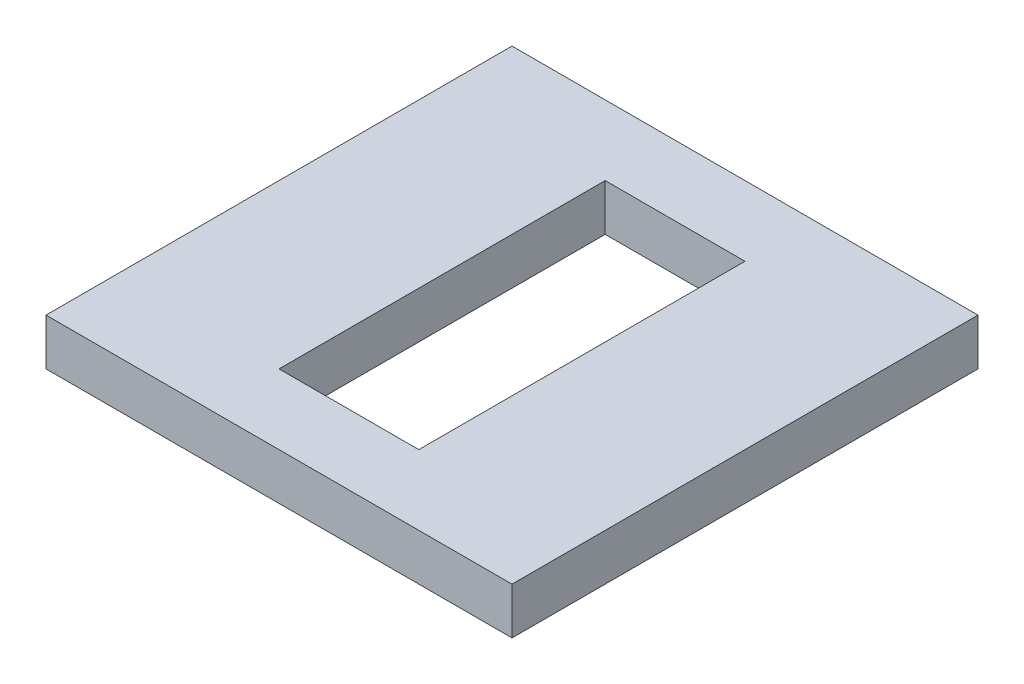
SolidWorks part; units mm, degrees
ref_plane "Front Plane" through (0, 0, 0) normal (0, 0, 1) x (1, 0, 0)
ref_plane "Top Plane" through (0, 0, 0) normal (0, 1, 0) x (1, 0, 0)
ref_plane "Right Plane" through (0, 0, 0) normal (1, 0, 0) x (0, 0, -1)
sketch "Sketch1" plane through (0, 0, 0) normal (0, 1, 0) x (1, 0, 0)
  line L1 (-49.3023, 40.5814) -> (50.6977, 40.5814)
  line L2 (-49.3023, 40.5814) -> (-49.3023, -59.4186)
  line L3 (-49.3023, -59.4186) -> (50.6977, -59.4186)
  line L4 (50.6977, 40.5814) -> (50.6977, -59.4186)
  line L5 (-14.3023, 25.5814) -> (15.6977, 25.5814)
  line L6 (-14.3023, 25.5814) -> (-14.3023, -44.4186)
  line L7 (-14.3023, -44.4186) -> (15.6977, -44.4186)
  line L8 (15.6977, 25.5814) -> (15.6977, -44.4186)
  dimension "D1" = 100
  dimension "D2" = 100
  dimension "D3" = 30
  dimension "D4" = 70
  dimension "D5" = 15
  dimension "D6" = 35
extrude "Boss-Extrude1" add sketch "Sketch1" along normal blind 10
